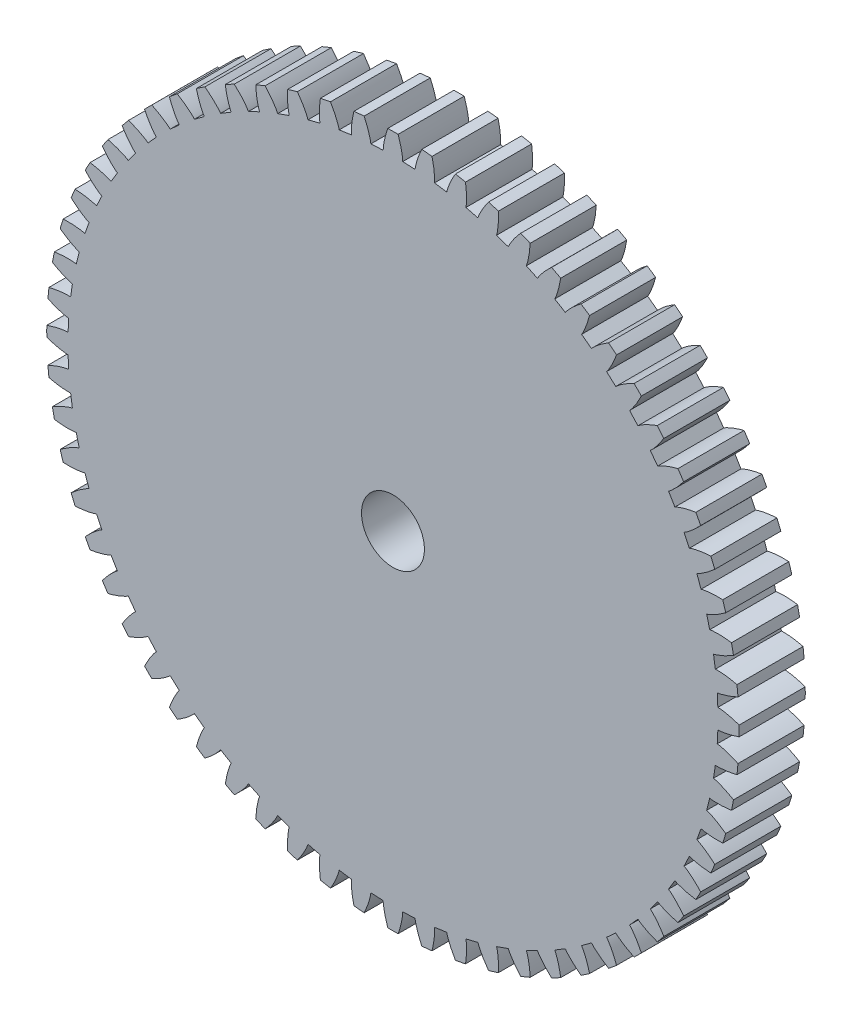
SolidWorks part; units mm, degrees
material "Plain Carbon Steel"
ref_plane "Front Plane" through (0, 0, 0) normal (0, 0, 1) x (1, 0, 0)
ref_plane "Top Plane" through (0, 0, 0) normal (0, 1, 0) x (1, 0, 0)
ref_plane "Right Plane" through (0, 0, 0) normal (1, 0, 0) x (0, 0, -1)
sketch "Sketch1" plane through (0, 0, 0) normal (0, 0, 1) x (1, 0, 0)
  circle A0 centre (0, 0) radius 52.3875
  dimension "D1" = 104.775
extrude "Boss-Extrude1" add sketch "Sketch1" along normal blind 10
sketch "Sketch2" plane through (0, 0, 0) normal (0, 0, 1) x (1, 0, 0)
  spline S0 degree 4 poles (49.1596, 1.4796) (49.1645, 1.4797) (49.1783, 1.4799) (49.2042, 1.4798) (49.2467, 1.4789) (49.3008, 1.4769) (49.3708, 1.4732) (49.4534, 1.4673) (49.5443, 1.4594) (49.6433, 1.4491) (49.7422, 1.4374) (49.841, 1.4244) (49.9396, 1.4103) (50.0592, 1.3917) (50.2028, 1.3674) (50.371, 1.3361) (50.5622, 1.2971) (50.7575, 1.2536) (50.9501, 1.2078) (51.1452, 1.158) (51.3344, 1.1072) (51.5315, 1.0509) (51.7136, 0.9971) (51.9184, 0.9327) (52.0839, 0.8796) (52.3029, 0.8051) (52.4325, 0.7599) (52.5844, 0.7054) (52.652, 0.6804) (52.6936, 0.6651) knots 0 0 0 0 0 0.005377 0.015084 0.028532 0.04661 0.064855 0.092111 0.119476 0.146842 0.174209 0.201575 0.228941 0.256307 0.307035 0.361767 0.4165 0.471232 0.525964 0.580697 0.635429 0.690161 0.744894 0.799626 0.854358 0.909091 0.954545 1 1 1 1 1 construction
  spline S1 degree 4 poles (49.1596, 1.4796) (49.1645, 1.4797) (49.1783, 1.4799) (49.2042, 1.4798) (49.2467, 1.4789) (49.3008, 1.4769) (49.3708, 1.4732) (49.4534, 1.4673) (49.5443, 1.4594) (49.6433, 1.4491) (49.7422, 1.4374) (49.841, 1.4244) (49.9396, 1.4103) (50.0592, 1.3917) (50.2028, 1.3674) (50.371, 1.3361) (50.5622, 1.2971) (50.7575, 1.2536) (50.9501, 1.2078) (51.1452, 1.158) (51.3344, 1.1072) (51.5315, 1.0509) (51.7136, 0.9971) (51.9184, 0.9327) (52.0839, 0.8796) (52.2554, 0.8213) (52.339, 0.7924) (52.3817, 0.7774) knots 0 0 0 0 0 0.005377 0.015084 0.028532 0.04661 0.064855 0.092111 0.119476 0.146842 0.174209 0.201575 0.228941 0.256307 0.307035 0.361767 0.4165 0.471232 0.525964 0.580697 0.635429 0.690161 0.744894 0.799626 0.854358 0.909091 0.909091 0.909091 0.909091 0.909091
  spline S2 degree 4 poles (49.0679, 3.346) (49.0728, 3.3464) (49.0865, 3.3476) (49.1123, 3.3502) (49.1545, 3.3552) (49.2081, 3.3625) (49.2774, 3.3731) (49.3591, 3.387) (49.4487, 3.4038) (49.5463, 3.4238) (49.6436, 3.4451) (49.7407, 3.4677) (49.8374, 3.4915) (49.9546, 3.5217) (50.0951, 3.5599) (50.2594, 3.6076) (50.4458, 3.6651) (50.6359, 3.7275) (50.8232, 3.792) (51.0125, 3.8607) (51.1957, 3.9297) (51.3863, 4.0051) (51.5624, 4.0765) (51.7599, 4.1607) (51.9193, 4.2298) (52.13, 4.3253) (52.2545, 4.3831) (52.4003, 4.4522) (52.4652, 4.4836) (52.5051, 4.503) knots 0 0 0 0 0 0.005377 0.015084 0.028532 0.04661 0.064855 0.092111 0.119476 0.146842 0.174209 0.201575 0.228941 0.256307 0.307035 0.361767 0.4165 0.471232 0.525964 0.580697 0.635429 0.690161 0.744894 0.799626 0.854358 0.909091 0.954545 1 1 1 1 1 construction
  spline S3 degree 4 poles (49.0679, 3.346) (49.0728, 3.3464) (49.0865, 3.3476) (49.1123, 3.3502) (49.1545, 3.3552) (49.2081, 3.3625) (49.2774, 3.3731) (49.3591, 3.387) (49.4487, 3.4038) (49.5463, 3.4238) (49.6436, 3.4451) (49.7407, 3.4677) (49.8374, 3.4915) (49.9546, 3.5217) (50.0951, 3.5599) (50.2594, 3.6076) (50.4458, 3.6651) (50.6359, 3.7275) (50.8232, 3.792) (51.0125, 3.8607) (51.1957, 3.9297) (51.3863, 4.0051) (51.5624, 4.0765) (51.7599, 4.1607) (51.9193, 4.2298) (52.0843, 4.3046) (52.1646, 4.3415) (52.2057, 4.3606) knots 0 0 0 0 0 0.005377 0.015084 0.028532 0.04661 0.064855 0.092111 0.119476 0.146842 0.174209 0.201575 0.228941 0.256307 0.307035 0.361767 0.4165 0.471232 0.525964 0.580697 0.635429 0.690161 0.744894 0.799626 0.854358 0.909091 0.909091 0.909091 0.909091 0.909091
  spline S4 degree 1 poles (49.0679, 3.346) (49.1596, 1.4796) knots 0 0 1 1 construction
  spline S5 degree 1 poles (49.0679, 3.346) (49.1596, 1.4796) knots 0 0 1 1
  spline S6 degree 1 poles (52.3817, 0.7774) (59.9934, 0.8904) knots 0 0 1 1 construction
  spline S7 degree 1 poles (52.3817, 0.7774) (59.9934, 0.8904) knots 0 0 1 1
  spline S8 degree 4 poles (59.9981, 0.4767) (59.9979, 0.5063) (59.9973, 0.5633) (59.9967, 0.6404) (59.9941, 0.8495) (59.9927, 0.941) (59.9881, 1.2106) (59.9845, 1.3636) (59.9793, 1.5848) (59.9741, 1.765) (59.9679, 1.9699) (59.9612, 2.1599) (59.9538, 2.3588) (59.9458, 2.5524) (59.9372, 2.7489) (59.9278, 2.9441) (59.918, 3.1392) (59.9073, 3.3356) (59.8963, 3.5291) (59.8842, 3.7277) (59.8722, 3.9174) (59.8583, 4.122) (59.8458, 4.3018) (59.8293, 4.5225) (59.8179, 4.6751) (59.7961, 4.9439) (59.7884, 5.0351) (59.7706, 5.2434) (59.7637, 5.3202) (59.7586, 5.377) (59.7559, 5.4064) knots 0 0 0 0 0 0.020959 0.041918 0.083333 0.123016 0.162698 0.202381 0.242063 0.281746 0.321429 0.361111 0.400794 0.440476 0.480159 0.519841 0.559524 0.599206 0.638889 0.678571 0.718254 0.757937 0.797619 0.837302 0.876984 0.916667 0.958082 0.979041 1 1 1 1 1 construction
  spline S9 degree 4 poles (59.9934, 0.8904) (59.9928, 0.9312) (59.9915, 1.0106) (59.9881, 1.2106) (59.9845, 1.3636) (59.9793, 1.5848) (59.9741, 1.765) (59.9679, 1.9699) (59.9612, 2.1599) (59.9538, 2.3588) (59.9458, 2.5524) (59.9372, 2.7489) (59.9278, 2.9441) (59.918, 3.1392) (59.9073, 3.3356) (59.8963, 3.5291) (59.8842, 3.7277) (59.8722, 3.9174) (59.8583, 4.122) (59.8458, 4.3018) (59.8293, 4.5225) (59.8179, 4.6751) (59.8017, 4.8745) (59.7952, 4.9536) (59.7918, 4.9943) knots 0.083333 0.083333 0.083333 0.083333 0.083333 0.123016 0.162698 0.202381 0.242063 0.281746 0.321429 0.361111 0.400794 0.440476 0.480159 0.519841 0.559524 0.599206 0.638889 0.678571 0.718254 0.757937 0.797619 0.837302 0.876984 0.916667 0.916667 0.916667 0.916667 0.916667
  spline S10 degree 1 poles (59.7918, 4.9943) (52.2057, 4.3606) knots 0 0 1 1 construction
  spline S11 degree 1 poles (59.7918, 4.9943) (52.2057, 4.3606) knots 0 0 1 1
extrude "Cut-Extrude2" cut sketch "Sketch2" against normal blind 11 and the other way blind 11
ref_axis "Axis1" through (0, 0, -0.5) along (0, 0, 1)
pattern_circular "CirPattern1" count 64 over 360 about axis through (0, 0, -0.5) along (0, 0, 1) of "Cut-Extrude2"
sketch "Sketch3" plane through (0, 0, 0) normal (0, 0, 1) x (1, 0, 0)
  circle A0 centre (0, 0) radius 4.7625
  dimension "D1" = 9.525
extrude "Cut-Extrude4" cut sketch "Sketch3" against normal blind 12 and the other way blind 12
